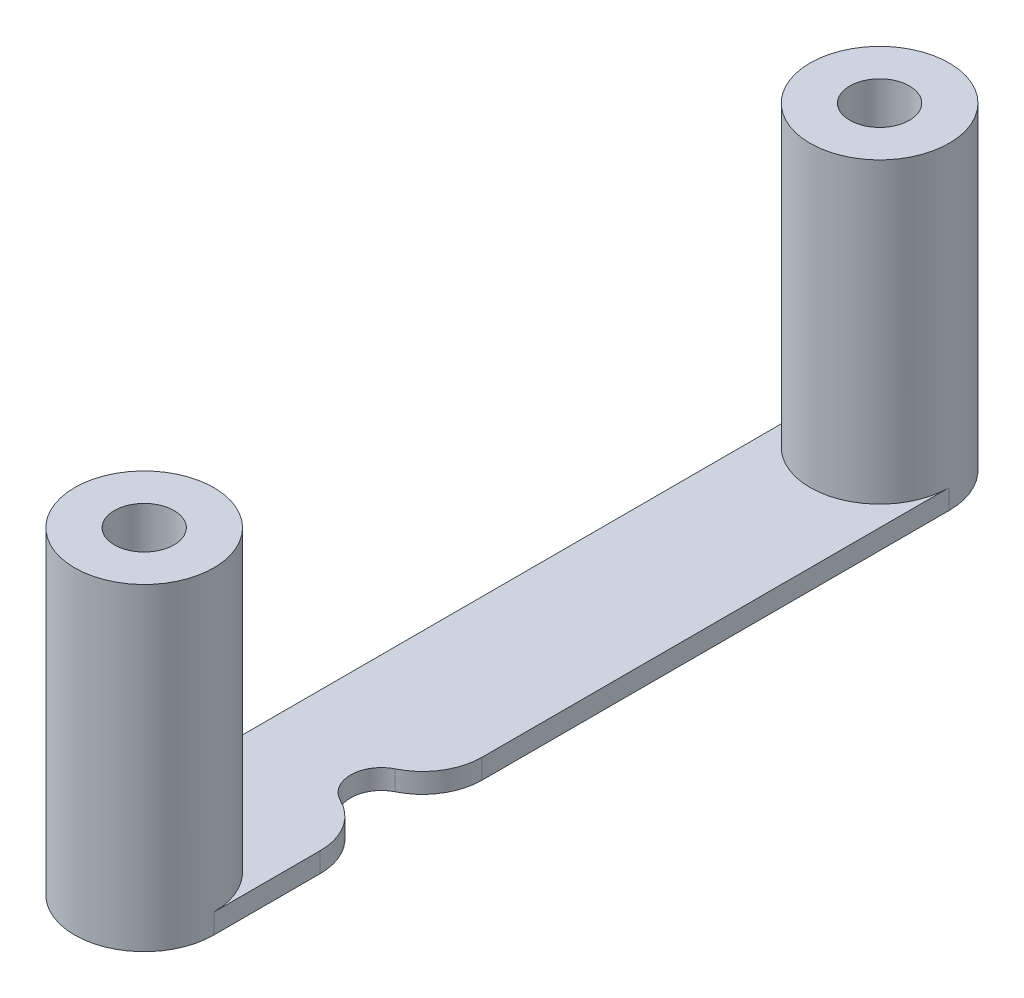
SolidWorks part; units mm, degrees
ref_plane "Front Plane" through (0, 0, 0) normal (0, 0, 1) x (1, 0, 0)
ref_plane "Top Plane" through (0, 0, 0) normal (0, 1, 0) x (1, 0, 0)
ref_plane "Right Plane" through (0, 0, 0) normal (1, 0, 0) x (0, 0, -1)
sketch "Sketch1" plane through (0, 0, 0) normal (0, 1, 0) x (1, 0, 0)
  line L0 (7, 3.5) -> (7, 40.5)
  line L1 (0.8683, 0) -> (3.5, 0)
  line L2 (0, 3.5) -> (0, 40.5)
  arc A0 (7, 40.5) -> (0, 40.5) centre (3.5, 40.5) ccw
  arc A1 (0, 3.5) -> (7, 3.5) centre (3.5, 3.5) ccw
  dimension "D1" = 3.5
  dimension "D2" = 37
  dimension "D3" = 7
extrude "Boss-Extrude1" add sketch "Sketch1" along normal blind 1 contours A1 L0 A0 L2 region at (3.5, 0, -22)
sketch "Sketch2" plane through (0, 1, 0) normal (0, 1, 0) x (1, 0, 0)
  circle A0 centre (3.5, 40.5) radius 3.5
  circle A3 centre (3.5, 3.5) radius 3.5
  dimension "D1" = 7
  dimension "D2" = 7
  dimension "D3" = 37
extrude "Boss-Extrude2" add sketch "Sketch2" along normal blind 15
sketch "Sketch5" plane through (0, 16, 0) normal (0, 1, 0) x (1, 0, 0)
  circle A5 centre (3.5, 3.5) radius 1.5
  circle A6 centre (3.5, 40.5) radius 1.5
  dimension "D3" = 3
  dimension "D4" = 3
extrude "Cut-Extrude3" cut sketch "Sketch5" along normal through all and the other way through all contours A5 | A6
sketch "Sketch6" plane through (0, 0, 0) normal (0, -1, 0) x (1, 0, 0)
  circle A0 centre (6, -12.928) radius 1.537 construction
  circle A1 centre (6, -12.928) radius 1.537
extrude "Cut-Extrude4" cut sketch "Sketch6" against normal up to next
fillet "Fillet1" radius 3 2 edges at (7, 0.5, -14.0952) (7, 0.5, -11.7608)
